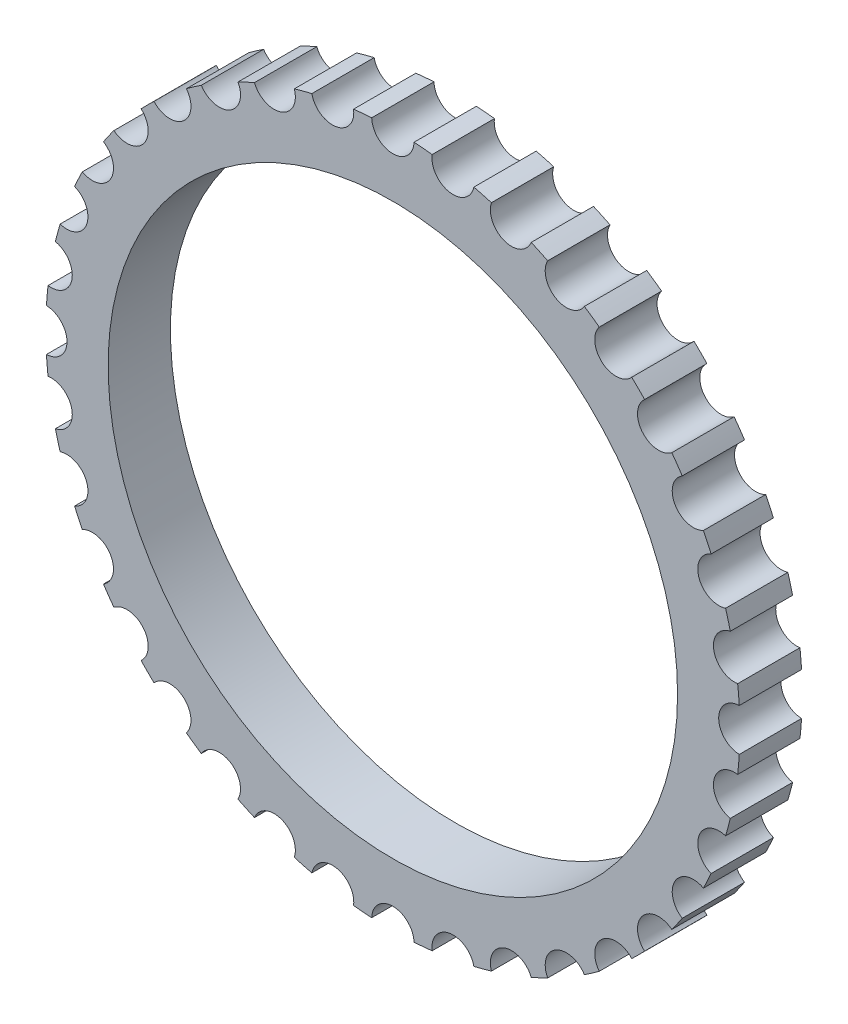
SolidWorks part; units mm, degrees
ref_plane "Front Plane" through (0, 0, 0) normal (0, 0, 1) x (1, 0, 0)
ref_plane "Top Plane" through (0, 0, 0) normal (0, 1, 0) x (1, 0, 0)
ref_plane "Right Plane" through (0, 0, 0) normal (1, 0, 0) x (0, 0, -1)
sketch "Sketch1" plane through (0, 0, 0) normal (0, 0, 1) x (1, 0, 0)
  circle A0 centre (0, 0) radius 22.8521
  circle A1 centre (0, 0) radius 27.8521
  dimension "D1" = 5
  dimension "D2" = 55.7042
extrude "Boss-Extrude1" add sketch "Sketch1" along normal blind 5
ref_plane "Plane1" through (0, 0, 2.5) normal (0, 0, 1) x (1, 0, 0)
sketch "Sketch2" plane through (0, 0, 2.5) normal (0, 0, 1) x (1, 0, 0)
  line L0 (15, 15) -> (-15, -15) construction
  line L1 (-15, -15) -> (15, -15) construction
  line L2 (-15, -15) -> (-15, 15) construction
  line L3 (-15, 15) -> (15, 15) construction
  line L4 (15, -15) -> (15, 15) construction
  circle A0 centre (-15, 15) radius 2.5
  circle A1 centre (15, 15) radius 2.5
  circle A2 centre (15, -15) radius 2.5
  circle A3 centre (-15, -15) radius 2.5
  point P4 (0, 0)
  dimension "D1" = 5
  dimension "D2" = 30
extrude "Boss-Extrude2" [suppressed] add sketch "Sketch2" along normal blind 15 and the other way blind 15
sketch "Sketch3" plane through (0, 0, 2.5) normal (0, 0, 1) x (1, 0, 0)
  circle A0 centre (0, 0) radius 27.8521 construction
  circle A1 centre (27.8521, 0) radius 1.7
  circle A2 centre (27.429, -4.8365) radius 1.7
  circle A3 centre (26.1724, -9.526) radius 1.7
  circle A4 centre (24.1206, -13.9261) radius 1.7
  circle A5 centre (21.336, -17.903) radius 1.7
  circle A6 centre (17.903, -21.336) radius 1.7
  circle A7 centre (13.9261, -24.1206) radius 1.7
  circle A8 centre (9.526, -26.1724) radius 1.7
  circle A9 centre (4.8365, -27.429) radius 1.7
  circle A10 centre (0, -27.8521) radius 1.7
  circle A11 centre (-4.8365, -27.429) radius 1.7
  circle A12 centre (-9.526, -26.1724) radius 1.7
  circle A13 centre (-13.9261, -24.1206) radius 1.7
  circle A14 centre (-17.903, -21.336) radius 1.7
  circle A15 centre (-21.336, -17.903) radius 1.7
  circle A16 centre (-24.1206, -13.9261) radius 1.7
  circle A17 centre (-26.1724, -9.526) radius 1.7
  circle A18 centre (-27.429, -4.8365) radius 1.7
  circle A19 centre (-27.8521, 0) radius 1.7
  circle A20 centre (-27.429, 4.8365) radius 1.7
  circle A21 centre (-26.1724, 9.526) radius 1.7
  circle A22 centre (-24.1206, 13.9261) radius 1.7
  circle A23 centre (-21.336, 17.903) radius 1.7
  circle A24 centre (-17.903, 21.336) radius 1.7
  circle A25 centre (-13.9261, 24.1206) radius 1.7
  circle A26 centre (-9.526, 26.1724) radius 1.7
  circle A27 centre (-4.8365, 27.429) radius 1.7
  circle A28 centre (0, 27.8521) radius 1.7
  circle A29 centre (4.8365, 27.429) radius 1.7
  circle A30 centre (9.526, 26.1724) radius 1.7
  circle A31 centre (13.9261, 24.1206) radius 1.7
  circle A32 centre (17.903, 21.336) radius 1.7
  circle A33 centre (21.336, 17.903) radius 1.7
  circle A34 centre (24.1206, 13.9261) radius 1.7
  circle A35 centre (26.1724, 9.526) radius 1.7
  circle A36 centre (27.429, 4.8365) radius 1.7
  point P75 (0, 0)
  dimension "D1" = 55.7042
  dimension "D2" = 3.4
  dimension "D3" = 36
extrude "Cut-Extrude1" cut sketch "Sketch3" against normal mid plane 16
